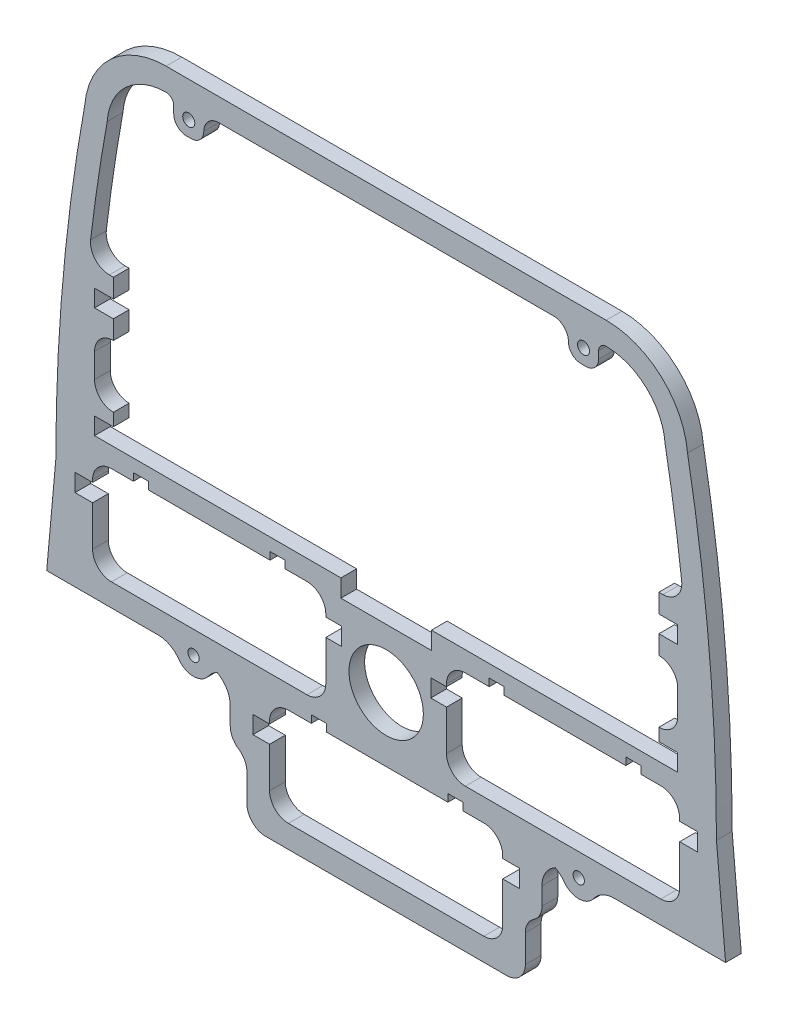
SolidWorks part; units mm, degrees
material "Delrin 2700 NC010, Low Viscosity Acetal Copolymer (SS)"
ref_plane "Front Plane" through (0, 0, 0) normal (0, 0, 1) x (1, 0, 0)
ref_plane "Top Plane" through (0, 0, 0) normal (0, 1, 0) x (1, 0, 0)
ref_plane "Right Plane" through (0, 0, 0) normal (1, 0, 0) x (0, 0, -1)
sketch "Sketch1" plane through (0, 0, 0) normal (0, 0, 1) x (1, 0, 0)
  line L0 (33.3676, -11.9888) -> (34.29, -22.225)
  line L1 (22.225, 27.94) -> (-22.225, 27.94)
  line L2 (-34.29, -22.225) -> (-30.4467, 20.4259) construction
  line L3 (-33.3676, -11.9888) -> (-33.3676, 14.6458) construction
  line L4 (-33.3676, -11.9888) -> (-34.29, -22.225)
  line L5 (16.9079, 25.654) -> (-16.9079, 25.654)
  line L6 (6.096, -13.97) -> (6.096, -19.939)
  line L7 (-29.6529, -19.939) -> (-6.096, -19.939)
  line L8 (-34.29, -22.225) -> (-21.299, -22.225)
  line L9 (-29.6529, -10.033) -> (-29.6529, -12.192)
  line L10 (18.4213, 24.1407) -> (18.4213, 24.1363)
  line L11 (19.6913, 22.8663) -> (20.1867, 22.8663)
  line L12 (21.4567, 24.1363) -> (21.4567, 24.8713)
  line L13 (-21.4567, 24.1363) -> (-21.4567, 24.8713)
  line L14 (-19.6913, 22.8663) -> (-20.1867, 22.8663)
  line L15 (-18.4213, 24.1407) -> (-18.4213, 24.1363)
  line L16 (29.4572, -8.001) -> (4.572, -8.001)
  line L17 (29.6529, -10.033) -> (25.7309, -10.033)
  line L18 (0, 18.415) -> (0, -18.415) construction
  line L19 (-1007.9925, 0) -> (48992.0075, 0) construction
  line L20 (-6.096, -10.033) -> (-10.2069, -10.033)
  line L21 (19.939, 24.384) -> (21.4567, 24.384) construction
  line L22 (6.096, -19.939) -> (29.6529, -19.939)
  line L23 (-6.096, -10.033) -> (-6.096, -12.192)
  line L24 (5.9491, -2.2098) -> (59.5431, -2.2098) construction
  line L25 (5.9491, -2.2098) -> (5.9491, -11.9888) construction
  line L26 (3.4091, -11.9888) -> (-3.4091, -11.9888) construction
  line L27 (59.5431, -2.2098) -> (59.5431, -11.9888) construction
  line L28 (-31.7887, -19.939) -> (31.7887, -19.939) construction
  line L29 (22.225, 25.654) -> (-22.225, 25.654) construction
  line L30 (-6.096, -19.939) -> (-6.1666, -19.9899)
  line L31 (29.4572, -6.2738) -> (27.5522, -6.2738)
  line L32 (27.5522, -6.2738) -> (27.5522, -5.0038)
  line L33 (-29.6529, -12.192) -> (-31.4309, -12.192)
  line L34 (27.5522, -5.0038) -> (29.4572, -5.0038)
  line L35 (29.4572, 1.27) -> (27.5522, 1.27)
  line L36 (27.5522, 1.27) -> (27.5522, 3.175)
  line L37 (27.5522, 3.175) -> (29.4572, 3.175)
  line L38 (29.4572, 4.9022) -> (27.5522, 4.9022)
  line L39 (19.939, 24.384) -> (18.4213, 24.384) construction
  line L40 (27.5522, 4.9022) -> (27.5522, 6.8072)
  line L41 (27.5522, 6.8072) -> (30.0922, 6.8072)
  line L42 (19.939, 24.384) -> (19.939, 22.8663) construction
  line L43 (6.096, -10.033) -> (6.096, -12.192)
  line L44 (-29.4572, -6.2738) -> (-29.4572, -8.001)
  line L45 (-29.4572, -6.2738) -> (-27.5522, -6.2738)
  line L46 (-27.5522, -6.2738) -> (-27.5522, -5.0038)
  line L47 (-27.5522, -5.0038) -> (-29.4572, -5.0038)
  line L48 (-29.4572, 1.27) -> (-29.4572, -5.0038)
  line L49 (-29.4572, 1.27) -> (-27.5522, 1.27)
  line L50 (-27.5522, 1.27) -> (-27.5522, 3.175)
  line L51 (-27.5522, 3.175) -> (-29.4572, 3.175)
  line L52 (-29.4572, 4.9022) -> (-29.4572, 3.175)
  line L53 (-31.4309, -12.192) -> (-31.4309, -13.97)
  line L54 (-31.4309, -13.97) -> (-29.6529, -13.97)
  line L55 (-6.096, -12.192) -> (-4.5069, -12.192)
  line L56 (-4.5069, -12.192) -> (-4.5069, -13.97)
  line L57 (-4.5069, -13.97) -> (-6.096, -13.97)
  line L58 (-29.6529, -10.033) -> (-29.6529, -19.939) construction
  line L59 (-29.6529, -14.986) -> (-33.4249, -14.986) construction
  line L60 (-29.6529, -14.986) -> (-0.4824, -14.986) construction
  line L61 (-6.096, -13.97) -> (-6.096, -19.939)
  line L62 (-29.6529, -19.939) -> (-29.6529, -13.97)
  line L63 (29.6529, -19.939) -> (29.6529, -13.97)
  line L64 (-31.0816, -12.0913) -> (-31.7887, -19.939) construction
  line L65 (29.6529, -10.033) -> (29.6529, -12.192)
  line L66 (31.4309, -13.97) -> (29.6529, -13.97)
  line L67 (31.4309, -12.192) -> (31.4309, -13.97)
  line L68 (29.6529, -12.192) -> (31.4309, -12.192)
  line L69 (6.096, -12.192) -> (4.5069, -12.192)
  line L70 (4.5069, -12.192) -> (4.5069, -13.97)
  line L71 (4.5069, -13.97) -> (6.096, -13.97)
  line L72 (29.4572, 4.9022) -> (29.4572, 3.175)
  line L73 (31.0816, -12.0913) -> (31.7887, -19.939) construction
  line L74 (29.4572, 1.27) -> (29.4572, -5.0038)
  line L75 (29.4572, -6.2738) -> (29.4572, -8.001)
  line L76 (-29.4572, 4.9022) -> (-27.5522, 4.9022)
  line L77 (-27.5522, 4.9022) -> (-27.5522, 6.8072)
  line L78 (-27.5522, 6.8072) -> (-30.0922, 6.8072)
  line L79 (-17.616, -22.225) -> (-15.7485, -22.225)
  line L80 (21.299, -22.225) -> (34.29, -22.225)
  line L81 (-34.29, -22.225) -> (34.29, -22.225) construction
  line L82 (-4.572, -8.001) -> (-4.572, -9.779)
  line L83 (-4.572, -9.779) -> (0, -9.779)
  line L84 (0, -9.779) -> (4.572, -9.779)
  line L85 (4.572, -9.779) -> (4.572, -8.001)
  line L86 (-4.572, -8.001) -> (-29.4572, -8.001)
  line L87 (-11.7784, -22.225) -> (-11.7784, -24.384)
  line L88 (-11.7784, -24.384) -> (-13.4625, -24.384)
  line L89 (-13.4625, -24.384) -> (-13.4625, -26.162)
  line L90 (-13.4625, -26.162) -> (-11.7784, -26.162)
  line L91 (-11.7784, -26.162) -> (-11.7784, -32.131)
  line L92 (-11.7784, -32.131) -> (11.7784, -32.131)
  line L93 (11.7784, -32.131) -> (11.7784, -26.162)
  line L94 (11.7784, -26.162) -> (13.4625, -26.162)
  line L95 (13.4625, -26.162) -> (13.4625, -24.384)
  line L96 (13.4625, -24.384) -> (11.7784, -24.384)
  line L97 (11.7784, -24.384) -> (11.7784, -22.225)
  line L98 (11.7784, -22.225) -> (-11.7784, -22.225) construction
  line L99 (0, -32.131) -> (0, -22.225) construction
  line L100 (-11.7784, -22.225) -> (-7.562, -22.225)
  line L101 (-15.7485, -22.098) -> (-15.7485, -28.448) construction
  line L102 (-15.7485, -22.225) -> (-15.7485, -28.448)
  line L103 (-15.7485, -28.448) -> (-14.0644, -28.448)
  line L104 (-14.0644, -28.448) -> (-14.0644, -34.417)
  line L105 (-14.0644, -34.417) -> (14.0644, -34.417)
  line L106 (14.0644, -34.417) -> (14.0644, -28.448)
  line L107 (14.0644, -28.448) -> (15.7485, -28.448)
  line L108 (15.7485, -28.448) -> (15.7485, -22.225)
  line L109 (15.7485, -22.225) -> (17.616, -22.225)
  line L110 (15.7485, -28.448) -> (15.7485, -22.098) construction
  line L111 (15.7485, -22.098) -> (14.0609, -22.098) construction
  line L112 (14.0609, -22.098) -> (14.0609, -22.098) construction
  line L113 (-14.0609, -22.098) -> (-14.0609, -22.098) construction
  line L114 (-14.0609, -22.098) -> (-15.7485, -22.098) construction
  line L115 (-11.7309, -10.033) -> (-24.0069, -10.033)
  line L116 (7.762, -22.2885) -> (6.238, -22.2885) construction
  line L117 (11.9309, -10.1918) -> (10.4069, -10.1918) construction
  line L118 (-24.0069, -10.1917) -> (-25.5309, -10.1917) construction
  line L119 (-25.5309, -10.033) -> (-29.6529, -10.033)
  line L120 (10.4069, -10.033) -> (6.096, -10.033)
  line L121 (-10.2069, -10.1918) -> (-11.7309, -10.1918) construction
  line L122 (25.7309, -10.1918) -> (24.2069, -10.1918) construction
  line L123 (24.2069, -10.033) -> (11.9309, -10.033)
  line L124 (7.762, -22.225) -> (11.7784, -22.225)
  line L125 (11.9309, -10.1918) -> (10.4069, -10.1918) construction
  line L126 (-24.0069, -10.1917) -> (-25.5309, -10.1917) construction
  line L127 (-6.038, -22.225) -> (6.238, -22.225)
  line L136 (-10.2069, -10.1918) -> (-11.7309, -10.1918) construction
  line L137 (25.7309, -10.1918) -> (24.2069, -10.1918) construction
  line L138 (-25.5309, -10.1917) -> (-25.5309, -9.271)
  line L139 (-25.5309, -9.271) -> (-24.0069, -9.271)
  line L140 (-24.0069, -9.271) -> (-24.0069, -10.1917)
  line L141 (-11.7309, -10.1918) -> (-11.7309, -9.271)
  line L142 (-11.7309, -9.271) -> (-10.2069, -9.271)
  line L143 (-10.2069, -9.271) -> (-10.2069, -10.1918)
  line L144 (10.4069, -10.1918) -> (10.4069, -9.271)
  line L145 (10.4069, -9.271) -> (11.9309, -9.271)
  line L146 (11.9309, -9.271) -> (11.9309, -10.1918)
  line L147 (24.2069, -10.1918) -> (24.2069, -9.271)
  line L152 (7.762, -22.2885) -> (6.238, -22.2885) construction
  line L153 (-6.038, -22.2885) -> (-7.562, -22.2885) construction
  line L154 (-6.038, -22.2885) -> (-7.562, -22.2885) construction
  line L155 (24.2069, -9.271) -> (25.7309, -9.271)
  line L156 (25.7309, -9.271) -> (25.7309, -10.1918)
  line L157 (-7.562, -22.2885) -> (-7.562, -21.463)
  line L158 (-7.562, -21.463) -> (-6.038, -21.463)
  line L159 (-6.038, -21.463) -> (-6.038, -22.2885)
  line L160 (6.238, -22.2885) -> (6.238, -21.463)
  line L161 (6.238, -21.463) -> (7.762, -21.463)
  line L162 (7.762, -21.463) -> (7.762, -22.2885)
  arc A0 (22.225, 27.94) -> (30.4467, 20.4259) centre (22.225, 19.685) cw
  arc A1 (-22.225, 27.94) -> (-30.4467, 20.4259) centre (-22.225, 19.685) ccw
  arc A2 (33.3676, -11.9888) -> (30.4467, 20.4259) centre (-147.9525, -11.9888) ccw
  circle A3 centre (0, -15.748) radius 3.7592
  circle A4 centre (19.4575, -22.225) radius 0.5715
  arc A5 (-33.3676, -11.9888) -> (-30.4467, 20.4259) centre (147.9525, -11.9888) cw
  arc A6 (-17.616, -22.225) -> (-21.299, -22.225) centre (-19.4575, -22.225) cw
  arc A7 (17.616, -22.225) -> (21.299, -22.225) centre (19.4575, -22.225) ccw
  arc A8 (20.1867, 22.8663) -> (21.4567, 24.1363) centre (20.1867, 24.1363) ccw
  circle A9 centre (-19.939, 24.384) radius 0.6096
  circle A10 centre (19.939, 24.384) radius 0.6096
  arc A11 (18.4213, 24.1363) -> (19.6913, 22.8663) centre (19.6913, 24.1363) ccw
  circle A12 centre (-19.4575, -22.225) radius 0.5715
  arc A13 (18.4213, 24.1407) -> (16.9079, 25.654) centre (16.9079, 24.1407) ccw
  arc A14 (22.2416, 25.654) -> (21.4567, 24.8713) centre (22.2394, 24.8713) ccw
  arc A15 (-22.2416, 25.654) -> (-21.4567, 24.8713) centre (-22.2394, 24.8713) cw
  arc A16 (-20.1867, 22.8663) -> (-21.4567, 24.1363) centre (-20.1867, 24.1363) cw
  arc A17 (-18.4213, 24.1363) -> (-19.6913, 22.8663) centre (-19.6913, 24.1363) cw
  arc A18 (-22.2416, 25.654) -> (-28.1777, 20.1262) centre (-22.225, 19.685) ccw
  arc A19 (-18.4213, 24.1407) -> (-16.9079, 25.654) centre (-16.9079, 24.1407) cw
  arc A20 (31.0816, -12.0913) -> (31.0816, -11.9888) centre (-147.9525, -11.9888) ccw
  circle A21 centre (-19.4575, -22.225) radius 1.8415 construction
  arc A23 (22.2416, 25.654) -> (28.1777, 20.1262) centre (22.225, 19.685) cw
  arc A25 (-22.225, 25.654) -> (-28.1777, 20.1262) centre (-22.225, 19.685) ccw construction
  arc A26 (22.225, 25.654) -> (28.1777, 20.1262) centre (22.225, 19.685) cw construction
  arc A28 (-31.0816, -12.0913) -> (-28.1777, 20.1262) centre (147.9525, -11.9888) cw construction
  arc A30 (31.0816, -12.0913) -> (28.1777, 20.1262) centre (-147.9525, -11.9888) ccw construction
  arc A31 (30.0922, 6.8072) -> (28.1777, 20.1262) centre (-147.9525, -11.9888) ccw
  arc A33 (-30.0922, 6.8072) -> (-28.1777, 20.1262) centre (147.9525, -11.9888) cw
  point P0 (0, 0)
  point P1 (0, 27.94)
  point P31 (0, -11.9888)
  point P121 (-30.9018, -14.986)
  point P135 (-17.616, -22.225)
  dimension "D4" = 2.286
  dimension "D6" = 8.255
  dimension "D7" = 19.4575
  dimension "D8" = 50.165
  dimension "D9" = 15.748
  dimension "D5" = 1.2192
  dimension "D17" = 1.143
  dimension "D3" = 7.5184
  dimension "D18" = 1.27
  dimension "D19" = 1.27
  dimension "D26" = 11.176
  dimension "D28" = 0.7827
  dimension "D29" = 1.5133
  dimension "D32" = 1.778
  dimension "D2" = 44.45
  dimension "D10" = 1.27
  dimension "D11" = 1.27
  dimension "D12" = 68.58
  dimension "D13" = 19.939
  dimension "D14" = 22.225
  dimension "D15" = 53.594
  dimension "D16" = 9.779
  dimension "D20" = 6.096
  dimension "D21" = 11.938
  dimension "D22" = 2.032
  dimension "D23" = 1.7272
  dimension "D24" = 1.27
  dimension "D25" = 1.905
  dimension "D27" = 0.4954
  dimension "D30" = 1.905
  dimension "D31" = 1.7272
  dimension "D33" = 1.778
  dimension "D34" = 2.159
  dimension "D35" = 23.5569
  dimension "D36" = 26.924
  dimension "D37" = 1.905
  dimension "D38" = 2.54
  dimension "D39" = 1.778
  dimension "D40" = 9.144
  dimension "D42" = 0.762
  dimension "D43" = 0.762
  dimension "D44" = 1.684
  dimension "D41" = 2.286
extrude "Boss-Extrude1" add sketch "Sketch1" along normal blind 1.5875 contours L8 A12 A4 L0 A2 A0 L1 A1 A5 L4 L74 L16 A18 A15 L13 A16 L14 A17 L15 A19 L5 A13 L10 A11 L11 A8 L12 A14 A23 A20 L22 L43 L17 A10 A9 A3 L20 region at (32.9056, -17.1901, 0)
ref_axis "Axis1" through (0, -15.748, 0) along (0, 0, 1)
fillet "Fillet1" radius 1.905 12 edges at (-6.096, -10.033, 0.7937) (-6.096, -19.939, 0.7937) (-29.6529, -19.939, 0.7937) (6.096, -19.939, 0.7937) (29.6529, -19.939, 0.7937) (29.6529, -10.033, 0.7937) (11.7784, -32.131, 0.7937) (-11.7784, -32.131, 0.7937) (-11.7784, -22.225, 0.7937) (11.7784, -22.225, 0.7937) (6.096, -10.033, 0.7937) (-29.6529, -10.033, 0.7937)
fillet "Fillet2" radius 1.905 6 edges at (-29.4572, 1.27, 0.7937) (-29.4572, -5.0038, 0.7937) (-30.0922, 6.8072, 0.7937) (29.4572, -5.0038, 0.7937) (29.4572, 1.27, 0.7937) (30.0922, 6.8072, 0.7937)
fillet "Fillet3" radius 2.54 6 edges at (-17.616, -22.225, 0.7937) (-21.299, -22.225, 0.7937) (21.299, -22.225, 0.7937) (17.616, -22.225, 0.7937) (15.7485, -22.225, 0.7937) (-15.7485, -22.225, 0.7937)
fillet "Fillet4" radius 1.905 4 edges at (15.7485, -28.448, 0.7937) (14.0644, -34.417, 0.7937) (-14.0644, -34.417, 0.7937) (-15.7485, -28.448, 0.7937)
fillet "Fillet5" radius 1.905 2 edges at (14.0644, -28.448, 0.7937) (-14.0644, -28.448, 0.7937)
